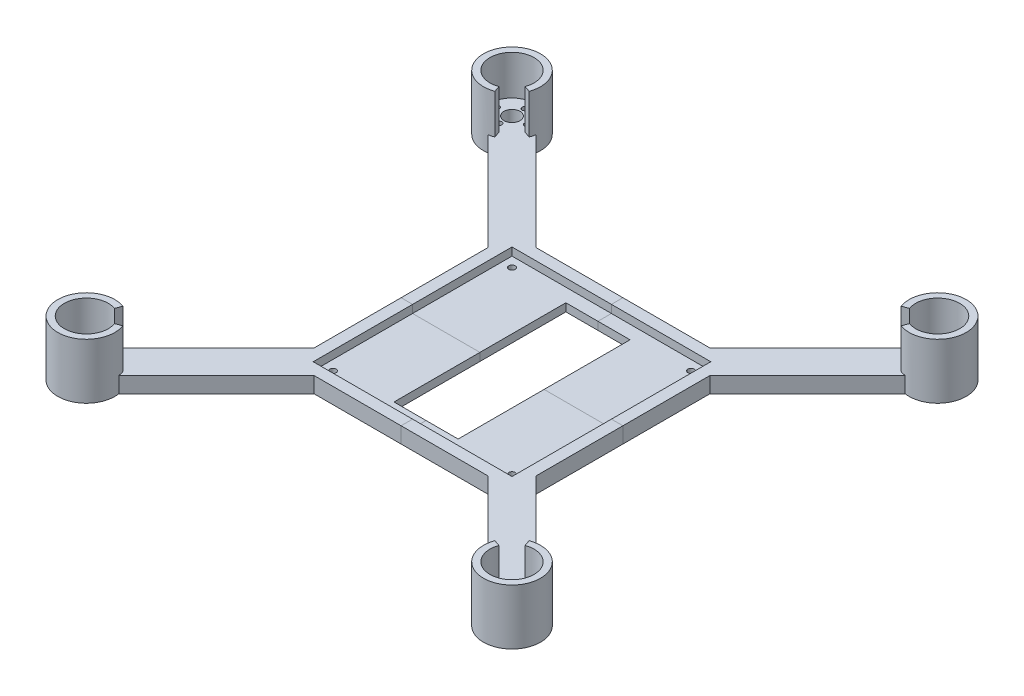
SolidWorks part; units mm, degrees
ref_plane "정면" through (0, 0, 0) normal (0, 0, 1) x (1, 0, 0)
ref_plane "윗면" through (0, 0, 0) normal (0, 1, 0) x (1, 0, 0)
ref_plane "우측면" through (0, 0, 0) normal (1, 0, 0) x (0, 0, -1)
sketch "스케치1" plane through (0, 0, 0) normal (0, 1, 0) x (1, 0, 0)
  line L0 (55, 70) -> (116.5668, 131.5668)
  line L1 (-55, 70) -> (55, 70)
  line L2 (-70, 55) -> (-70, -55)
  line L3 (-55, -70) -> (55, -70)
  line L4 (70, 55) -> (70, -55)
  line L5 (-60.2755, 60.2755) -> (60.2245, -60.2245) construction
  line L6 (-77.3477, -77.3477) -> (43.1523, 43.1523) construction
  line L7 (-20.25, 54.25) -> (20.25, 54.25)
  line L8 (-20.25, 54.25) -> (-20.25, -54.25)
  line L9 (-20.25, -54.25) -> (20.25, -54.25)
  line L10 (20.25, 54.25) -> (20.25, -54.25)
  line L11 (-20.25, 54.25) -> (20.25, -54.25) construction
  line L12 (-20.25, -54.25) -> (20.25, 54.25) construction
  line L13 (70, 55) -> (131.5668, 116.5668)
  line L14 (116.3503, 134.3503) -> (152.3503, 134.3503) construction
  line L15 (134.3503, 152.3503) -> (134.3503, 116.3503) construction
  line L16 (147.0782, 121.6224) -> (121.6224, 147.0782) construction
  line L17 (70, -55) -> (131.5668, -116.5668)
  line L18 (55, -70) -> (116.5668, -131.5668)
  line L19 (134.3503, -116.3503) -> (134.3503, -152.3503) construction
  line L20 (152.3503, -134.3503) -> (116.3503, -134.3503) construction
  line L21 (121.6224, -147.0782) -> (147.0782, -121.6224) construction
  line L22 (-55, -70) -> (-116.5668, -131.5668)
  line L23 (-70, -55) -> (-131.5668, -116.5668)
  line L24 (-116.3503, -134.3503) -> (-152.3503, -134.3503) construction
  line L25 (-134.3503, -152.3503) -> (-134.3503, -116.3503) construction
  line L26 (-147.0782, -121.6224) -> (-121.6224, -147.0782) construction
  line L27 (-70, 55) -> (-131.5668, 116.5668)
  line L28 (-55, 70) -> (-116.5668, 131.5668)
  line L29 (-134.3503, 116.3503) -> (-134.3503, 152.3503) construction
  line L30 (-152.3503, 134.3503) -> (-116.3503, 134.3503) construction
  line L31 (-121.6224, 147.0782) -> (-147.0782, 121.6224) construction
  line L32 (55, 70) -> (70, 70) construction
  line L33 (70, 70) -> (70, 55) construction
  line L34 (55, -70) -> (70, -70) construction
  line L35 (70, -55) -> (70, -70) construction
  line L36 (-70, -70) -> (-55, -70) construction
  line L37 (-70, -55) -> (-70, -70) construction
  line L38 (-70, 70) -> (-70, 55) construction
  line L39 (-70, 70) -> (-55, 70) construction
  line L45 (-56.5, 56.5) -> (56.5, -56.5) construction
  line L46 (-56.5, -56.5) -> (56.5, 56.5) construction
  circle A0 centre (-56.5, -56.5) radius 2
  circle A1 centre (56.5, -56.5) radius 2
  circle A2 centre (56.5, 56.5) radius 2
  circle A3 centre (-56.5, 56.5) radius 2
  arc A4 (131.5668, 116.5668) -> (116.5668, 131.5668) centre (134.3503, 134.3503) ccw
  arc A5 (116.5668, 131.5668) -> (121.6224, 121.6224) centre (134.3503, 134.3503) ccw construction
  arc A6 (121.6224, 121.6224) -> (131.5668, 116.5668) centre (134.3503, 134.3503) ccw construction
  circle A11 centre (134.3503, 124.8503) radius 1.65
  circle A12 centre (126.3503, 134.3503) radius 1.65
  circle A13 centre (142.3503, 134.3503) radius 1.65
  circle A14 centre (134.3503, 143.8503) radius 1.65
  circle A15 centre (134.3503, 134.3503) radius 5.1
  arc A16 (116.5668, -131.5668) -> (131.5668, -116.5668) centre (134.3503, -134.3503) ccw
  circle A17 centre (124.8503, -134.3503) radius 1.65
  circle A18 centre (134.3503, -126.3503) radius 1.65
  circle A19 centre (134.3503, -142.3503) radius 1.65
  circle A20 centre (143.8503, -134.3503) radius 1.65
  circle A21 centre (134.3503, -134.3503) radius 5.1
  arc A22 (131.5668, -116.5668) -> (121.6224, -121.6224) centre (134.3503, -134.3503) ccw construction
  arc A23 (121.6224, -121.6224) -> (116.5668, -131.5668) centre (134.3503, -134.3503) ccw construction
  arc A24 (-131.5668, -116.5668) -> (-116.5668, -131.5668) centre (-134.3503, -134.3503) ccw
  circle A25 centre (-134.3503, -124.8503) radius 1.65
  circle A26 centre (-126.3503, -134.3503) radius 1.65
  circle A27 centre (-142.3503, -134.3503) radius 1.65
  circle A28 centre (-134.3503, -143.8503) radius 1.65
  circle A29 centre (-134.3503, -134.3503) radius 5.1
  arc A30 (-116.5668, -131.5668) -> (-121.6224, -121.6224) centre (-134.3503, -134.3503) ccw construction
  arc A31 (-121.6224, -121.6224) -> (-131.5668, -116.5668) centre (-134.3503, -134.3503) ccw construction
  arc A32 (-116.5668, 131.5668) -> (-131.5668, 116.5668) centre (-134.3503, 134.3503) ccw
  circle A33 centre (-124.8503, 134.3503) radius 1.65
  circle A34 centre (-134.3503, 126.3503) radius 1.65
  circle A35 centre (-134.3503, 142.3503) radius 1.65
  circle A36 centre (-143.8503, 134.3503) radius 1.65
  circle A37 centre (-134.3503, 134.3503) radius 5.1
  arc A38 (-131.5668, 116.5668) -> (-121.6224, 121.6224) centre (-134.3503, 134.3503) ccw construction
  arc A39 (-121.6224, 121.6224) -> (-116.5668, 131.5668) centre (-134.3503, 134.3503) ccw construction
  point P0 (0, 0)
  point P6 (0, 0)
  point P28 (0, 54.25)
  point P32 (134.3503, 134.3503)
  point P38 (134.3503, 134.3503)
  point P47 (-47.6793, 47.6793)
  point P48 (0, 0)
  point P57 (134.3503, -134.3503)
  point P63 (134.3503, -134.3503)
  point P80 (-134.3503, -134.3503)
  point P86 (-134.3503, -134.3503)
  point P103 (-134.3503, 134.3503)
  point P109 (-134.3503, 134.3503)
  point P118 (-55.4142, -55.4142)
  point P119 (0, 0)
  point P120 (0, 0)
  point P121 (-55.4142, 55.4142)
  point P122 (-56.1954, -56.1954)
  point P123 (0, 0)
  point P124 (55, -55)
  point P125 (50.5244, 50.5244)
  point P126 (0, 0)
  point P127 (0, 0)
  point P128 (56, -56)
  point P129 (55.9511, 55.9511)
  point P130 (0, 0)
  point P131 (0, 0)
  point P132 (0, 0)
  dimension "D5" = 4
  dimension "D13" = 36
  dimension "D14" = 3.3
  dimension "D15" = 8
  dimension "D16" = 16
  dimension "D19" = 10.2
  dimension "D1" = 140
  dimension "D2" = 140
  dimension "D3" = 108.5
  dimension "D4" = 40.5
  dimension "D6" = 56.5
  dimension "D10" = 15
  dimension "D11" = 15
  dimension "D12" = 190
  dimension "D17" = 9.5
  dimension "D18" = 19
  dimension "D20" = 4
extrude "보스-돌출1" add sketch "스케치1" against normal blind 10
sketch "스케치3" plane through (0, 0, 0) normal (0, 1, 0) x (1, 0, 0)
  line L0 (0, 0) -> (134.3503, 134.3503) construction
  line L1 (134.3503, 134.3503) -> (117.4358, 128.1939)
  line L2 (128.1939, 117.4358) -> (134.3503, 134.3503)
  circle A0 centre (134.3503, 134.3503) radius 13.9
  circle A1 centre (134.3503, 134.3503) radius 18
  arc A2 (117.4358, 128.1939) -> (128.1939, 117.4358) centre (134.3503, 134.3503) ccw
  arc M49 (131.5668, 116.5668) -> (116.5668, 131.5668) centre (134.3503, 134.3503) ccw
  dimension "D1" = 27.8
  dimension "D2" = 25
  dimension "D4" = 36
  dimension "D3" = 25
extrude "보스-돌출2" add sketch "스케치3" along normal blind 25 contours A1 L1 A0 L2 M49 region at (119.1881, 0, -129.3735)
ref_axis "기준축1" through (0, 26.25, 0) along (0, -1, 0)
pattern_circular "원형 패턴1" count 4 over 360 about axis through (0, 26.25, 0) along (0, -1, 0) of "보스-돌출2"
sketch "스케치4" plane through (0, 0, 0) normal (0, 1, 0) x (1, 0, 0)
  line L1 (-62.75, 62.75) -> (62.75, 62.75)
  line L2 (-62.75, 62.75) -> (-62.75, -62.75)
  line L3 (-62.75, -62.75) -> (62.75, -62.75)
  line L4 (62.75, 62.75) -> (62.75, -62.75)
  line L5 (-62.75, 62.75) -> (62.75, -62.75) construction
  line L6 (-62.75, -62.75) -> (62.75, 62.75) construction
  point P0 (0, 0)
  dimension "D1" = 125.5
  dimension "D2" = 125.5
extrude "컷-돌출1" cut sketch "스케치4" against normal blind 5
sketch "스케치5" plane through (0, 0, 0) normal (0, 1, 0) x (1, 0, 0)
  line L0 (0, 249.2054) -> (0, -249.2054)
  line L1 (-210.8279, 0) -> (210.8279, 0)
  point P4 (0, 0)
  point P8 (0, 0)
split "분할1" trim tools "스케치5" bodies to split 104 resulting bodies 105 106 107 108
